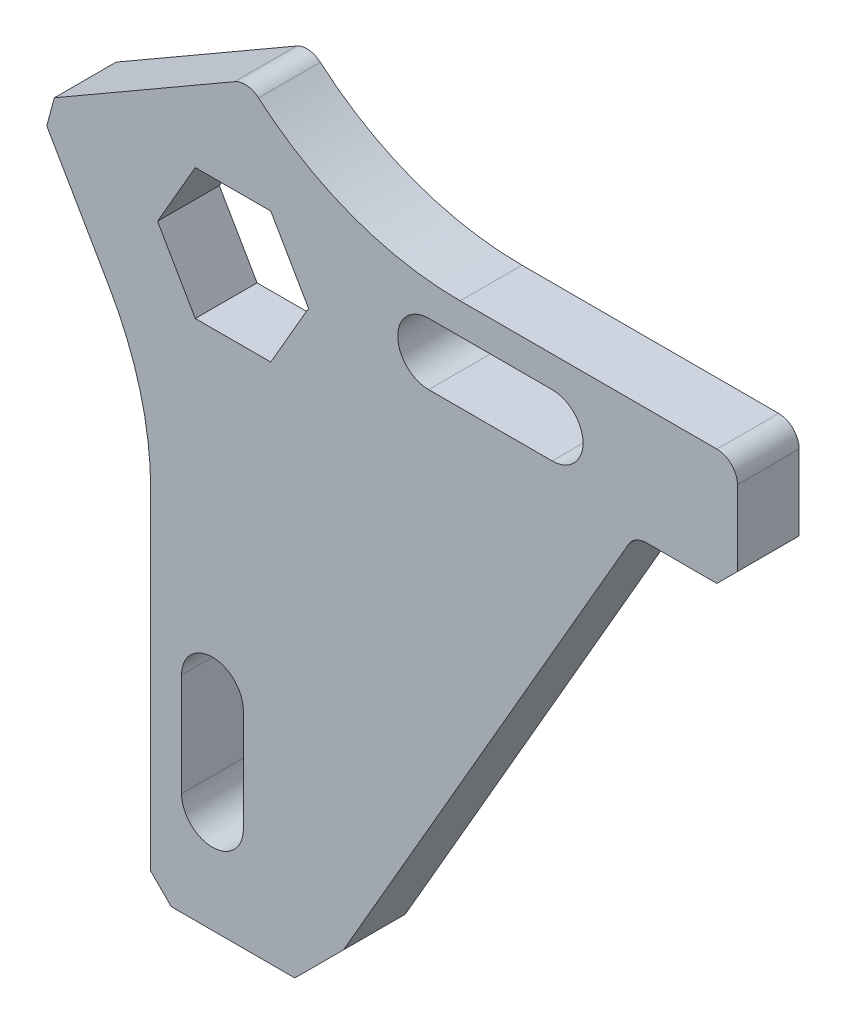
SolidWorks part; units mm, degrees
ref_plane "Plano frontal" through (0, 0, 0) normal (0, 0, 1) x (1, 0, 0)
ref_plane "Plano superior" through (0, 0, 0) normal (0, 1, 0) x (1, 0, 0)
ref_plane "Plano direito" through (0, 0, 0) normal (1, 0, 0) x (0, 0, -1)
sketch "Esboço1" plane through (0, 0, 0) normal (0, 0, 1) x (1, 0, 0)
  line L0 (0, 0) -> (0, 65)
  line L1 (0, 65) -> (47, 65)
  line L2 (47, 65) -> (47, 53.6936)
  line L3 (47, 53.6936) -> (16, 0)
  line L4 (16, 0) -> (0, 0)
  line L5 (6, 20) -> (6, 10) construction
  line L6 (4.3338, 50.65) -> (11.6662, 50.65)
  line L7 (11.6662, 50.65) -> (15.3323, 57)
  line L8 (15.3323, 57) -> (11.6662, 63.35)
  line L9 (11.6662, 63.35) -> (4.3338, 63.35)
  line L10 (4.3338, 63.35) -> (0.6677, 57)
  line L11 (0.6677, 57) -> (4.3338, 50.65)
  line L12 (9, 20) -> (9, 10)
  line L13 (3, 20) -> (3, 10)
  line L14 (27, 59) -> (39, 59) construction
  line L15 (27, 62) -> (39, 62)
  line L16 (27, 56) -> (39, 56)
  circle A0 centre (8, 57) radius 6.35 construction
  arc A1 (9, 20) -> (3, 20) centre (6, 20) ccw
  arc A2 (3, 10) -> (9, 10) centre (6, 10) ccw
  arc A3 (27, 62) -> (27, 56) centre (27, 59) ccw
  arc A4 (39, 56) -> (39, 62) centre (39, 59) ccw
  point P7 (6, 15)
  point P21 (33, 59)
  dimension "D3" = 12.7
  dimension "D9" = 3
  dimension "D11" = 8
  dimension "D14" = 3
  dimension "D1" = 8
  dimension "D2" = 8
  dimension "D4" = 65
  dimension "D5" = 47
  dimension "D6" = 16
  dimension "D7" = 60
  dimension "D8" = 6
  dimension "D10" = 12
  dimension "D12" = 6
  dimension "D13" = 10
  dimension "D15" = 50
extrude "Ressalto-extrusão1" add sketch "Esboço1" along normal blind 6
sketch "Esboço2" plane through (0, 0, 6) normal (0, 0, 1) x (1, 0, 0)
  line L0 (14.1776, 65) -> (9.4312, 73.2212)
  line L1 (47, 65) -> (0, 65) construction
  line L2 (9.4312, 73.2212) -> (-11.0936, 61.3712)
  line L3 (-11.0936, 61.3712) -> (0, 42.1564)
  line L4 (0, 65) -> (0, 0) construction
  line L5 (0, 42.1564) -> (0, 65)
  line L6 (0, 65) -> (14.1776, 65)
  line L7 (0.6677, 57) -> (4.3338, 50.65) construction
  line L8 (15.3323, 57) -> (11.6662, 63.35) construction
  dimension "D1" = 8
  dimension "D2" = 3
  dimension "D3" = 6
extrude "Ressalto-extrusão2" add sketch "Esboço2" against normal through all
fillet "Filete1" radius 30 2 edges at (0, 42.1564, 3) (14.1776, 65, 3)
chamfer "Chanfro1" distance 2 angle 45 4 edges at (16, 0, 3) (0, 0, 3) (-11.0936, 61.3712, 3) (47, 65, 3) first distance on face at (8, 0, 3) first distance on face at (0, 17.059, 3) first distance on face at (-7.5564, 55.2445, 3) first distance on face at (47, 59.3468, 3)
fillet "Filete2" radius 2 1 edges at (9.4312, 73.2212, 3)
sketch "Esboço3" plane through (0, 0, 6) normal (0, 0, 1) x (1, 0, 0)
  line L0 (45, 65) -> (57, 65)
  line L1 (57, 65) -> (57, 53.6936)
  line L2 (57, 53.6936) -> (47, 53.6936)
  line L3 (47, 53.6936) -> (47, 63)
  line L4 (47, 63) -> (45, 65)
  dimension "D1" = 12
extrude "Ressalto-extrusão3" add sketch "Esboço3" against normal through all
fillet "Filete3" radius 2 2 edges at (47, 53.6936, 3) (57, 65, 3)
chamfer "Chanfro2" distance 2 angle 45 1 edges at (57, 53.6936, 3)
